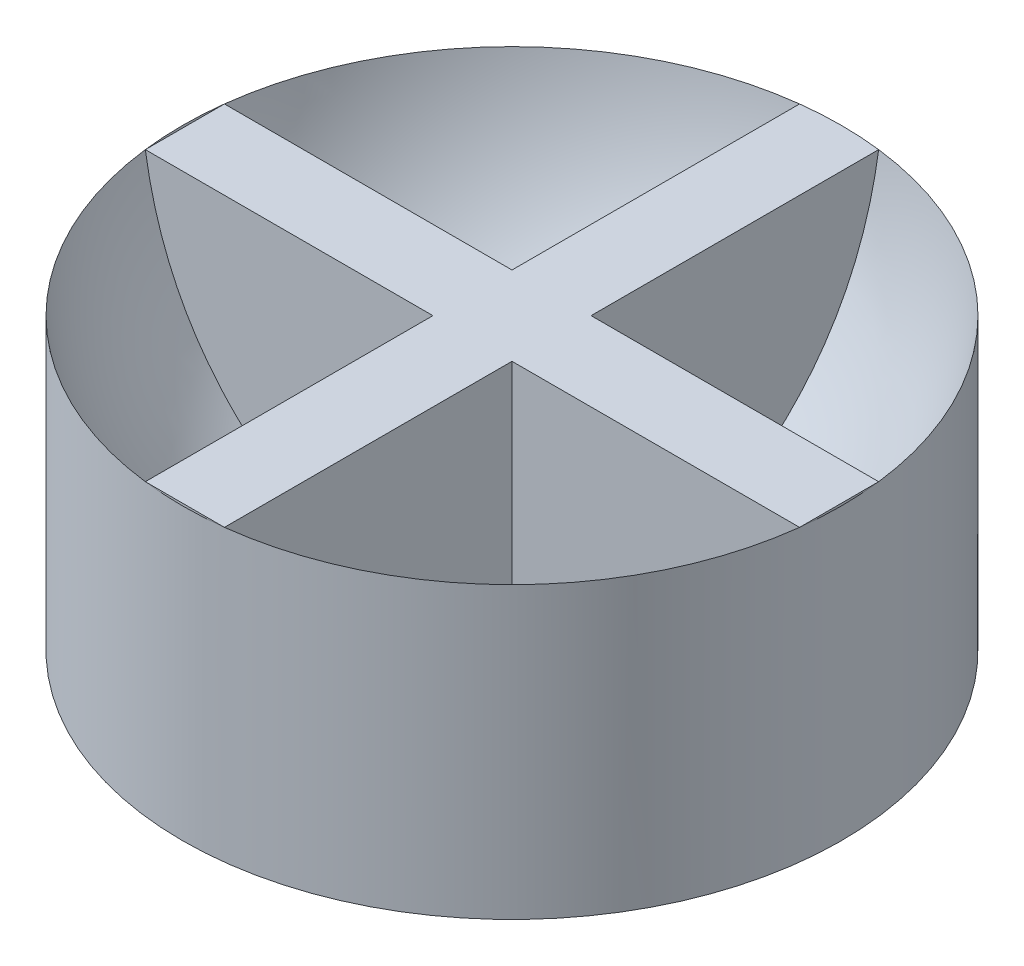
SolidWorks part; units mm, degrees
ref_plane "Front Plane" through (0, 0, 0) normal (0, 0, 1) x (1, 0, 0)
ref_plane "Top Plane" through (0, 0, 0) normal (0, 1, 0) x (1, 0, 0)
ref_plane "Right Plane" through (0, 0, 0) normal (1, 0, 0) x (0, 0, -1)
sketch "Sketch1" plane through (0, 0, 0) normal (0, 1, 0) x (1, 0, 0)
  circle A0 centre (0, 0) radius 62.5
  dimension "D1" = 125
extrude "Boss-Extrude1" add sketch "Sketch1" along normal blind 10
sketch "Sketch5" plane through (0, 0, 0) normal (1, 0, 0) x (0, 0, -1)
  line L0 (0, 0) -> (0, 44.7433) construction
  line L1 (-62.5, 55) -> (-62.5, 10)
  line L2 (-62.5, 0) -> (-62.5, 48.3968) construction
  line L3 (-62.5, 10) -> (-32.5, 10)
  line L5 (62.5, 10) -> (-62.5, 10) construction
  spline S0 degree 2 poles (-62.5, 55) (-57.9054, 24.9374) (-32.5, 10) knots 0 0 0 1 1 1
  point P5 (0, 0)
  dimension "D1" = 45
  dimension "D2" = 15
  dimension "D3" = 30
  dimension "D4" = 25
revolve "Revolve1" add sketch "Sketch5" angle 360 about L0
ref_plane "Plane2" through (0, 55, 0) normal (0, 1, 0) x (1, 0, 0)
sketch "Sketch7" plane through (0, 10, 0) normal (0, 1, 0) x (1, 0, 0)
  line L0 (7.5, 7.5) -> (7.5, 62.0484)
  line L2 (-7.5, 62.0484) -> (-7.5, 7.5)
  line L3 (-7.5, 7.5) -> (7.5, 7.5) construction
  line L4 (7.5, -7.5) -> (62.0484, -7.5)
  line L5 (62.0484, -7.5) -> (62.0484, 7.5)
  line L6 (62.0484, 7.5) -> (7.5, 7.5)
  line L7 (-7.5, -7.5) -> (-7.5, -62.0484)
  line L8 (-7.5, -62.0484) -> (7.5, -62.0484)
  line L9 (7.5, -62.0484) -> (7.5, -7.5)
  line L10 (-7.5, 7.5) -> (-62.0484, 7.5)
  line L11 (-62.0484, 7.5) -> (-62.0484, -7.5)
  line L12 (-62.0484, -7.5) -> (-7.5, -7.5)
  circle A0 centre (0, 0) radius 62.5 construction
  arc A1 (-7.5, 62.0484) -> (7.5, 62.0484) centre (0, 0) cw
  point P2 (0, 7.5)
  point P21 (0, 0)
  circle M4 centre (0, 0) radius 32.5
  dimension "D1" = 7.5
  dimension "D2" = 15
  dimension "D4" = 4
extrude "Boss-Extrude2" add sketch "Sketch7" along normal up to surface (45 mm away) contours L11 L12 L10 M4 | L3 L10 L12 L7 L9 L4 L6 M4 | L2 L3 L0 M4 | L2 L0 M4 | L5 L6 L4 M4 | L8 L9 L7 M4 region at (0, 10, -19.856) region at (0, 10, 5.5048) region at (0, 10, -47.2786) region at (47.1276, 10, 0) region at (-47.1276, 10, 0) region at (0, 10, 47.1276) up to plane "Plane2"
sketch "Sketch8" plane through (0, 10, 0) normal (0, 1, 0) x (1, 0, 0)
  line L0 (-27.8553, 7.5) -> (-7.5, 27.8553) construction
  line L1 (-7.5, 7.5) -> (-31.6228, 7.5) construction
  line L4 (-17.6777, 17.6777) -> (0, 0) construction
  line L5 (-7.5, 7.5) -> (-62.0484, 7.5) construction
  line L6 (-7.5, 7.5) -> (-7.5, 31.6228) construction
  circle A1 centre (-16.4756, 16.4756) radius 0.375
  circle A3 centre (-18.8798, 18.8798) radius 0.375
  circle A4 centre (16.4756, 16.4756) radius 0.375
  circle A5 centre (18.8798, 18.8798) radius 0.375
  circle A6 centre (16.4756, -16.4756) radius 0.375
  circle A7 centre (18.8798, -18.8798) radius 0.375
  circle A8 centre (-16.4756, -16.4756) radius 0.375
  circle A9 centre (-18.8798, -18.8798) radius 0.375
  point P0 (-17.6777, 17.6777)
  point P1 (-17.6777, 17.6777)
  point P22 (17.6777, 17.6777)
  point P27 (17.6777, -17.6777)
  point P32 (-17.6777, -17.6777)
  point P37 (0, 0)
  dimension "D2" = 45
  dimension "D4" = 0.75
  dimension "D1" = 25
  dimension "D3" = 1.7
  dimension "D5" = 4
extrude "Cut-Extrude1" cut sketch "Sketch8" against normal through all
